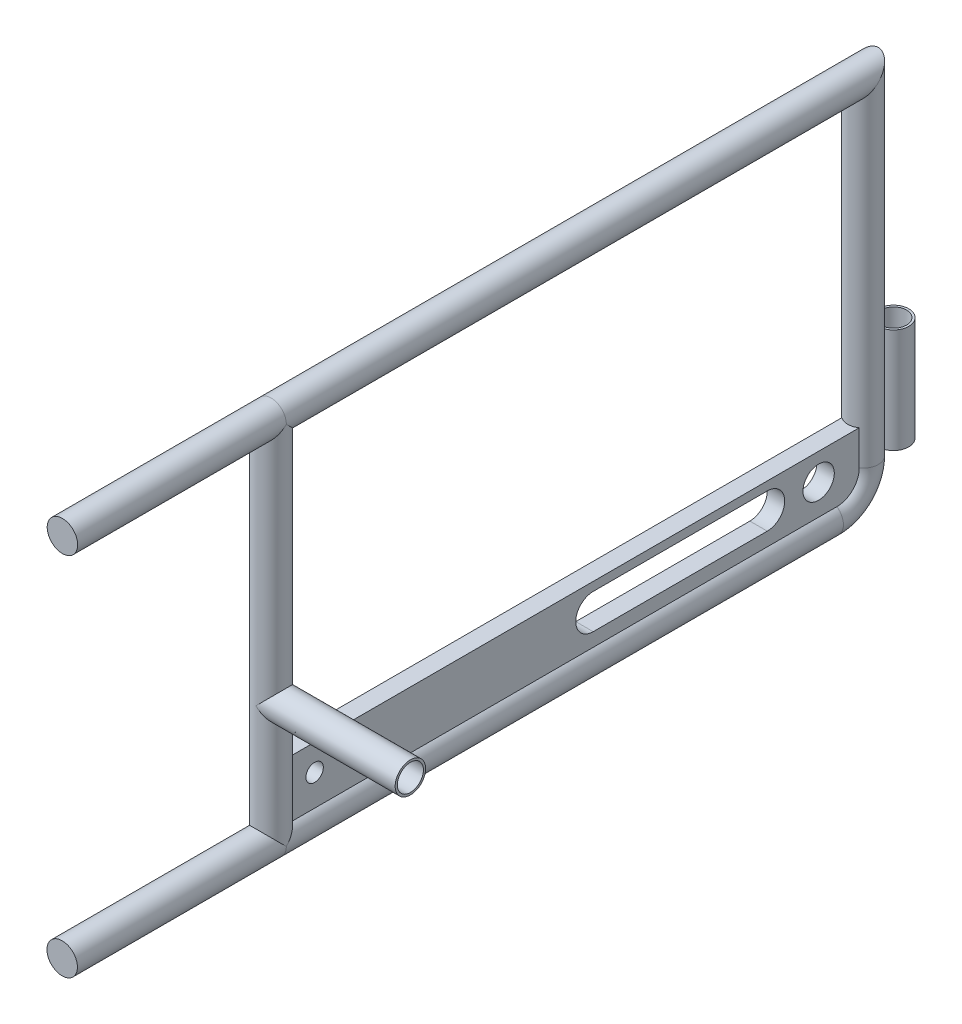
SolidWorks part; units mm, degrees
note: The reader was unsure of these and kept them because the rebuilt part matched: shared geometry of "Sketch3<8>", "Sketch1<23>".
ref_plane "Front Plane" through (0, 0, 0) normal (0, 0, 1) x (1, 0, 0)
ref_plane "Top Plane" through (0, 0, 0) normal (0, 1, 0) x (1, 0, 0)
ref_plane "Right Plane" through (0, 0, 0) normal (1, 0, 0) x (0, 0, -1)
sketch "Sketch1" plane through (0, 0, 0) normal (1, 0, 0) x (0, 0, -1)
  line L0 (126.1633, -30.1592) -> (152.2128, -152.4)
  line L2 (152.2128, -431.8) -> (584.0128, -431.8)
  line L4 (584.0128, -673.1) -> (584.0128, -431.8)
  line L5 (152.2128, -431.8) -> (0, -431.8)
  line L6 (558.6128, -698.5) -> (152.2128, -698.5)
  line L7 (88.9, 0) -> (0, 0)
  line L8 (152.2128, -152.4) -> (431.6128, -152.4)
  line L10 (457.0128, -177.8) -> (457.0128, -273.05)
  line L16 (457.0128, -273.05) -> (558.6128, -273.05)
  line L17 (584.0128, -298.45) -> (584.0128, -431.8)
  line L18 (-0.1872, -698.5) -> (152.2128, -698.5)
  line L19 (152.2128, -698.5) -> (152.2128, -431.8)
  line L20 (152.2128, -152.4) -> (152.2128, -431.8)
  arc A0 (88.9, 0) -> (126.1633, -30.1592) centre (88.9, -38.1) cw
  arc A1 (584.0128, -673.1) -> (558.6128, -698.5) centre (558.6128, -673.1) cw
  arc A2 (584.0128, -298.45) -> (558.6128, -273.05) centre (558.6128, -298.45) ccw
  arc A3 (431.6128, -152.4) -> (457.0128, -177.8) centre (431.6128, -177.8) cw
  point P5 (584.0128, -698.5)
  point P24 (584.0128, -273.05)
  point P30 (457.0128, -152.4)
  dimension "D2" = 38.1
  dimension "D11" = 25.4
  dimension "D9" = 25.4
  dimension "D1" = 88.9
  dimension "D3" = 120.65
  dimension "D4" = 431.8
  dimension "D5" = 431.8
  dimension "D6" = 279.4
  dimension "D7" = 152.4
  dimension "D8" = 546.1
  dimension "D10" = 127
  dimension "D17" = 124.9856
sketch "Sketch3" plane through (0, 0, 0) normal (0, 0, 1) x (1, 0, 0)
  circle A0 centre (0, -698.5) radius 11.1125
  dimension "D1" = 22.225
sweep "Sweep1" add profiles "Sketch3" path "Sketch1"
sweep "Sweep2" add profiles "Sketch3<8>" path "Sketch1<23>"
sketch "Sketch3<8>" plane through (0, 0, 0) normal (0, 0, 1) x (1, 0, 0) same geometry as "Sketch3"
sketch "Sketch1<23>" plane through (0, 0, 0) normal (1, 0, 0) x (0, 0, -1) same geometry as "Sketch1"
sketch "Sketch10" plane through (0, 0, 0) normal (1, 0, 0) x (0, 0, -1)
  line L1 (152.4, -914.4) -> (-272.7134, -914.4)
  line L2 (152.2128, -698.5) -> (152.2128, -431.8) construction
  circle A0 centre (152.2128, -609.6) radius 304.8
  dimension "D1" = 609.6
  dimension "D2" = 88.9
sketch "Sketch11" plane through (0, 0, 0) normal (1, 0, 0) x (0, 0, -1)
  line L0 (584.0128, -647.7) -> (152.2128, -647.7)
  line L1 (584.0128, -673.1) -> (584.0128, -431.8) construction
  line L2 (152.2128, -698.5) -> (152.2128, -431.8) construction
  line L3 (152.2128, -647.7) -> (152.2128, -698.5)
  line L4 (152.2128, -698.5) -> (558.6128, -698.5)
  line L5 (584.0128, -673.1) -> (584.0128, -647.7)
  line L6 (584.0128, -431.8) -> (584.0128, -482.6)
  line L7 (584.0128, -482.6) -> (152.2128, -482.6)
  line L8 (152.2128, -482.6) -> (152.2128, -431.8)
  line L9 (152.2128, -431.8) -> (584.0128, -431.8)
  line L10 (380.8128, -463.55) -> (177.6128, -666.75) construction
  line L11 (389.793, -472.5303) -> (186.593, -675.7303)
  line L12 (371.8325, -454.5697) -> (168.6325, -657.7697)
  line L13 (380.8128, -666.75) -> (177.6128, -463.55) construction
  line L14 (371.8325, -675.7303) -> (168.6325, -472.5303)
  line L15 (389.793, -657.7697) -> (186.593, -454.5697)
  line L16 (380.8128, -463.55) -> (507.8128, -463.55) construction
  line L17 (380.8128, -450.85) -> (507.8128, -450.85)
  line L18 (380.8128, -476.25) -> (507.8128, -476.25)
  line L19 (380.8128, -666.75) -> (507.8128, -666.75) construction
  line L20 (380.8128, -654.05) -> (507.8128, -654.05)
  line L21 (380.8128, -679.45) -> (507.8128, -679.45)
  line L22 (177.6128, -463.55) -> (177.6128, -666.75) construction
  line L23 (177.6128, -565.15) -> (446.4211, -666.75) construction
  line L24 (177.6128, -666.75) -> (446.4211, -565.15) construction
  line L25 (177.6128, -532.9233) -> (431.9175, -666.75) construction
  line L26 (431.9175, -666.75) -> (431.9175, -532.9233) construction
  line L27 (431.9175, -532.9233) -> (177.6128, -666.75) construction
  arc A0 (584.0128, -673.1) -> (558.6128, -698.5) centre (558.6128, -673.1) cw
  circle A1 centre (177.6128, -463.55) radius 6.35
  circle A2 centre (177.6128, -666.75) radius 6.35
  circle A3 centre (279.2128, -565.15) radius 6.35
  arc A4 (380.8128, -450.85) -> (380.8128, -476.25) centre (380.8128, -463.55) ccw
  arc A5 (389.793, -472.5303) -> (371.8325, -454.5697) centre (380.8128, -463.55) ccw
  arc A6 (168.6325, -657.7697) -> (186.593, -675.7303) centre (177.6128, -666.75) ccw
  arc A7 (371.8325, -675.7303) -> (389.793, -657.7697) centre (380.8128, -666.75) ccw
  arc A8 (186.593, -454.5697) -> (168.6325, -472.5303) centre (177.6128, -463.55) ccw
  arc A9 (507.8128, -476.25) -> (507.8128, -450.85) centre (507.8128, -463.55) ccw
  arc A10 (380.8128, -654.05) -> (380.8128, -679.45) centre (380.8128, -666.75) ccw
  arc A11 (507.8128, -679.45) -> (507.8128, -654.05) centre (507.8128, -666.75) ccw
  arc A12 (380.8128, -463.55) -> (464.982, -666.75) centre (177.6064, -666.7541) cw
  point P12 (584.0128, -698.5)
  point P27 (279.2128, -565.15)
  point P32 (279.2128, -565.15)
  point P39 (444.3128, -463.55)
  point P44 (444.3128, -666.75)
  dimension "D1" = 25.4
  dimension "D4" = 12.7
  dimension "D5" = 12.7
  dimension "D8" = 12.7
  dimension "D12" = 287.3756
  dimension "D2" = 50.8
  dimension "D3" = 50.8
  dimension "D6" = 19.05
  dimension "D7" = 19.05
  dimension "D9" = 90
  dimension "D10" = 25.4
  dimension "D11" = 76.2
extrude "Boss-Extrude2" add sketch "Sketch11" along normal mid plane 12.7 contours A2 | L0 L3 L4 A0 L5 | L21 A11 L20 A10
sketch "Sketch12" plane through (0, 0, 0) normal (1, 0, 0) x (0, 0, -1)
  circle A0 centre (152.2128, -609.6) radius 11.1125
  circle A1 centre (152.2128, -609.6) radius 9.525
  dimension "D1" = 19.05
  dimension "D2" = 22.225
extrude "Boss-Extrude3" add sketch "Sketch12" along normal blind 101.6
ref_plane "Plane1" through (0, -673.1, 0) normal (0, 1, 0) x (1, 0, 0)
sketch "Sketch13" plane through (0, -673.1, 0) normal (0, 1, 0) x (1, 0, 0)
  circle A0 centre (0, 606.2378) radius 11.1125
  circle A1 centre (0, 606.2378) radius 9.525
  arc A2 (6.35, 574.8933) -> (-6.35, 574.8933) centre (0, 584.0128) ccw construction
  dimension "D1" = 19.05
  dimension "D2" = 22.225
extrude "Boss-Extrude4" add sketch "Sketch13" along normal blind 76.2 separate body
sketch "Sketch14" plane through (0, 0, 0) normal (1, 0, 0) x (0, 0, -1)
  circle A0 centre (545.2695, -667.2317) radius 11.43
  dimension "D1" = 22.86
extrude "Cut-Extrude2" cut sketch "Sketch14" against normal through all both and the other way through all contours A0
